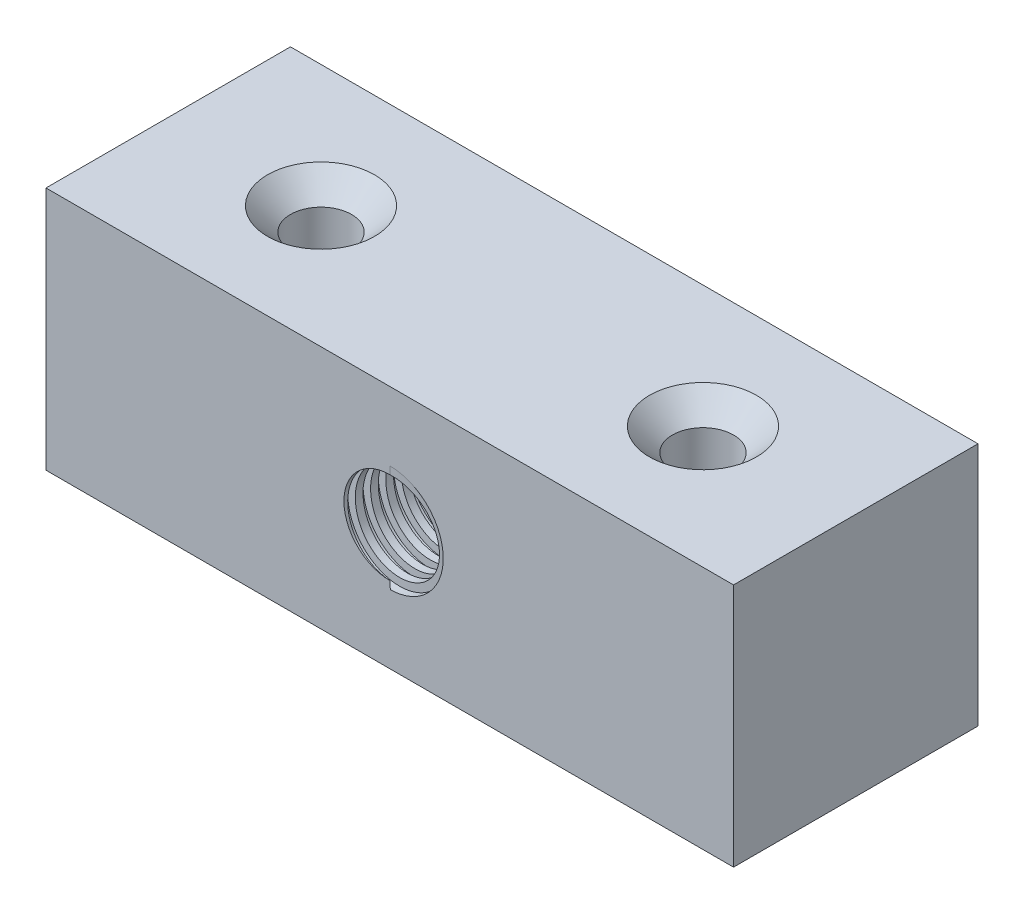
SolidWorks part; units mm, degrees
material "Chrome Stainless Steel"
ref_plane "Front Plane" through (0, 0, 0) normal (0, 0, 1) x (1, 0, 0)
ref_plane "Top Plane" through (0, 0, 0) normal (0, 1, 0) x (1, 0, 0)
ref_plane "Right Plane" through (0, 0, 0) normal (1, 0, 0) x (0, 0, -1)
sketch "Sketch1" plane through (0, 0, 0) normal (0, 0, 1) x (1, 0, 0)
  line L1 (-45, 16) -> (45, 16)
  line L2 (-45, 16) -> (-45, -16)
  line L3 (-45, -16) -> (45, -16)
  line L4 (45, 16) -> (45, -16)
  line L5 (-45, 16) -> (45, -16) construction
  line L6 (-45, -16) -> (45, 16) construction
  point P0 (0, 0)
  dimension "D1" = 90
  dimension "D2" = 32
extrude "Boss-Extrude1" add sketch "Sketch1" along normal blind 32
hole_wizard "Ø1.0mm Dowel Hole1" positions "Sketch2" profile "Sketch3" hole size "Ø1.0" standard "ANSI Metric" end condition up to next
sketch "Sketch2" plane through (0, 0, 32) normal (0, 0, 1) x (1, 0, 0)
  point P0 (0, 0)
sketch "Sketch3" plane through (0, 0, 32) normal (1, 0, 0) x (0, -1, 0)
  line L0 (0, 0) -> (0, 32)
  line L1 (0, 32) -> (6, 32)
  line L2 (6, 32) -> (6, 0)
  line L5 (6, 0) -> (0, 0)
  line L11 (0, -6.35) -> (0, 107.95) construction
  dimension "Thru Hole Dia." = 12
  dimension "Thru Hole Depth" = 32
hole_wizard "Ø1.0mm Dowel Hole2" positions "Sketch4" profile "Sketch5" hole size "Ø1.0" standard "ANSI Metric" end condition up to next
sketch "Sketch4" plane through (0, 16, 0) normal (0, 1, 0) x (1, 0, 0)
  line L0 (45, -32) -> (45, 0) construction
  point P0 (25, -16)
  point P2 (-25, -16)
  point P7 (45, -16)
  dimension "D1" = 50
  dimension "D2" = 20
sketch "Sketch5" plane through (25, 16, 16) normal (1, 0, 0) x (0, 0, 1)
  line L0 (0, 0) -> (0, 32)
  line L1 (0, 32) -> (4, 32)
  line L2 (4, 32) -> (4, 0)
  line L5 (4, 0) -> (0, 0)
  line L11 (0, -6.35) -> (0, 107.95) construction
  dimension "Thru Hole Dia." = 8
  dimension "Thru Hole Depth" = 32
chamfer "Chamfer1" distance 3 angle 45 2 edges at (-25, 16, 20) (25, 16, 20)
sketch "Sketch6" plane through (0, 0, 32) normal (0, 0, 1) x (1, 0, 0)
  circle A0 centre (0, 0) radius 6 construction
  circle A1 centre (0, 0) radius 6
curve "Helix/Spiral1" pitch 2 height 34 radius 6 centre (0, 0, 32) axis (0, 0, -1) start towards (1, 0, 0)
ref_plane "Plane1" through (6, 0, 32) normal (0, -0.9986, -0.053) x (-1, 0, 0)
sketch "Sketch7" plane through (6, 0, 32) normal (0, -0.9986, -0.053) x (-1, 0, 0)
  line L1 (12.9979, 3.5127) -> (10.9979, 3.5127)
  line L2 (12.9979, 3.5127) -> (12.9979, 2.5127)
  line L3 (12.9979, 2.5127) -> (10.9979, 2.5127)
  line L4 (10.9979, 3.5127) -> (10.9979, 2.5127)
  line L5 (12.9979, 3.5127) -> (10.9979, 2.5127) construction
  line L6 (12.9979, 2.5127) -> (10.9979, 3.5127) construction
  point P0 (11.9979, 3.0127)
  dimension "D1" = 1
  dimension "D2" = 2
sweep "Cut-Sweep1" cut profiles "Sketch7" path "Helix/Spiral1" align with end faces yes
